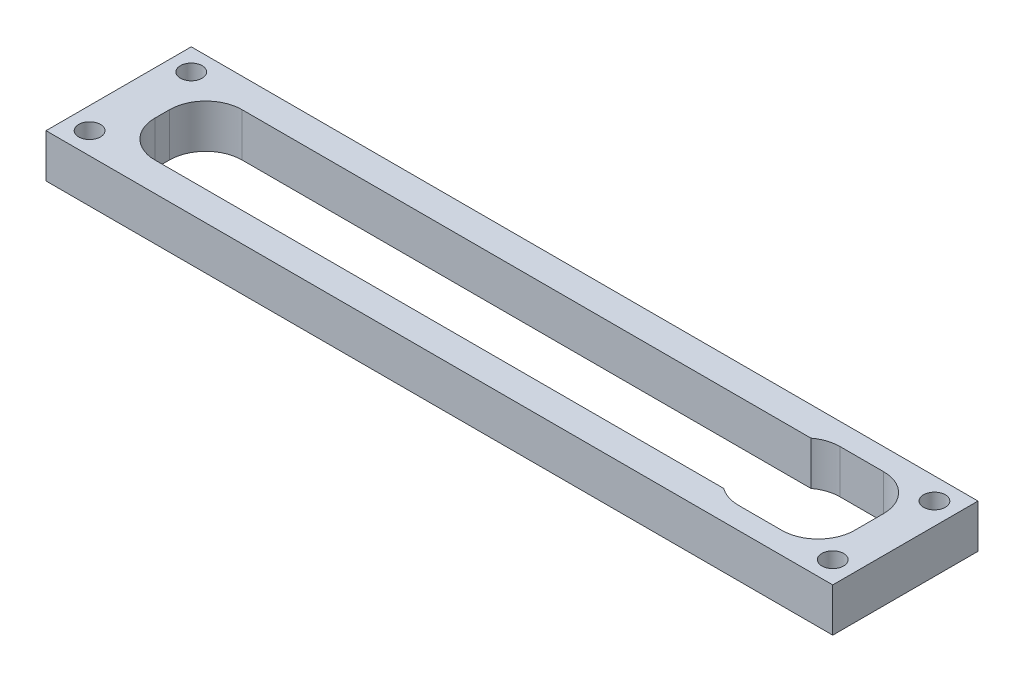
SolidWorks part; units mm, degrees
ref_plane "Front Plane" through (0, 0, 0) normal (0, 0, 1) x (1, 0, 0)
ref_plane "Top Plane" through (0, 0, 0) normal (0, 1, 0) x (1, 0, 0)
ref_plane "Right Plane" through (0, 0, 0) normal (1, 0, 0) x (0, 0, -1)
sketch "Sketch1" plane through (0, 0, 0) normal (0, 1, 0) x (1, 0, 0)
  line L0 (54.1604, 20) -> (54.1604, 0) construction
  line L1 (0, 0) -> (108.3209, 0)
  line L2 (0, 0) -> (0, 20)
  line L3 (0, 20) -> (108.3209, 20)
  line L4 (108.3209, 0) -> (108.3209, 20)
  line L5 (0, 10) -> (108.3209, 10) construction
  line L6 (54.1604, 16) -> (54.1604, 4) construction
  line L7 (6, 16) -> (102.3209, 16)
  line L8 (6, 16) -> (6, 4)
  line L9 (6, 4) -> (102.3209, 4)
  line L10 (102.3209, 16) -> (102.3209, 4)
  line L11 (6, 10) -> (102.3209, 10) construction
  circle A0 centre (3, 17) radius 1.5
  circle A1 centre (3, 3) radius 1.5
  circle A2 centre (105.3209, 3) radius 1.5
  circle A3 centre (105.3209, 17) radius 1.5
  point P17 (54.1604, 10)
  point P18 (54.1604, 10)
  dimension "D7" = 3
  dimension "D1" = 108.3209
  dimension "D2" = 20
  dimension "D3" = 96.3209
  dimension "D4" = 12
  dimension "D5" = 3
  dimension "D6" = 3
extrude "Boss-Extrude1" add sketch "Sketch1" along normal blind 6
sketch "Sketch2" plane through (0, 6, 0) normal (0, 1, 0) x (1, 0, 0)
  line L0 (92, 10) -> (-49908, 10) construction
  line L1 (102.3209, 4) -> (102.3209, 16) construction
  line L2 (89.3209, 17) -> (89.3209, 16)
  line L5 (102.3209, 16) -> (6, 16) construction
  line L6 (96.3209, 17) -> (96.3209, 3) construction
  line L7 (89.3209, 17) -> (103.3209, 17)
  line L9 (89.3209, 3) -> (103.3209, 3)
  line L10 (103.3209, 17) -> (103.3209, 3)
  line L12 (89.3209, 16) -> (102.3209, 16)
  line L13 (102.3209, 16) -> (102.3209, 4)
  line L14 (102.3209, 4) -> (89.3209, 4)
  line L15 (6, 4) -> (102.3209, 4) construction
  line L16 (89.3209, 4) -> (89.3209, 3)
  point P4 (102.3209, 10)
  point P23 (96.3209, 10)
  dimension "D1" = 1
  dimension "D2" = 14
  dimension "D3" = 14
extrude "Cut-Extrude1" cut sketch "Sketch2" against normal through all
fillet "Fillet1" radius 5 6 edges at (103.3209, 3, -17) (103.3209, 3, -3) (89.3209, 3, -17) (89.3209, 3, -3) (6, 3, -4) (6, 3, -16)
equation "\"TrackLength\"= ( ( \"n\" * 28 ) ) / cos ( \"MountAngle\" ) - ( 2 * \"x\" )"
equation "\"D1@Sketch1\"=\"TrackLength\""
equation "\"TrackWidth\"= \"MarbleTrackWidth\" + ( 2 * 4 )"
equation "\"D2@Sketch1\"=\"TrackWidth\""
equation "\"MarbleTrackWidth\"= \"MarbleWidth\" - 1"
equation "\"MarbleTrackLength\"= \"TrackLength\" - ( 2 * 6 )"
equation "\"D3@Sketch1\"=\"MarbleTrackLength\""
equation "\"D4@Sketch1\"=\"MarbleTrackWidth\""
equation "\"MarbleWidth\"= 13"
equation "\"n\"= 4"
equation "\"MountAngle\"= 5"
equation "\"x\"= 14 / cos ( \"MountAngle\" ) - 12"
